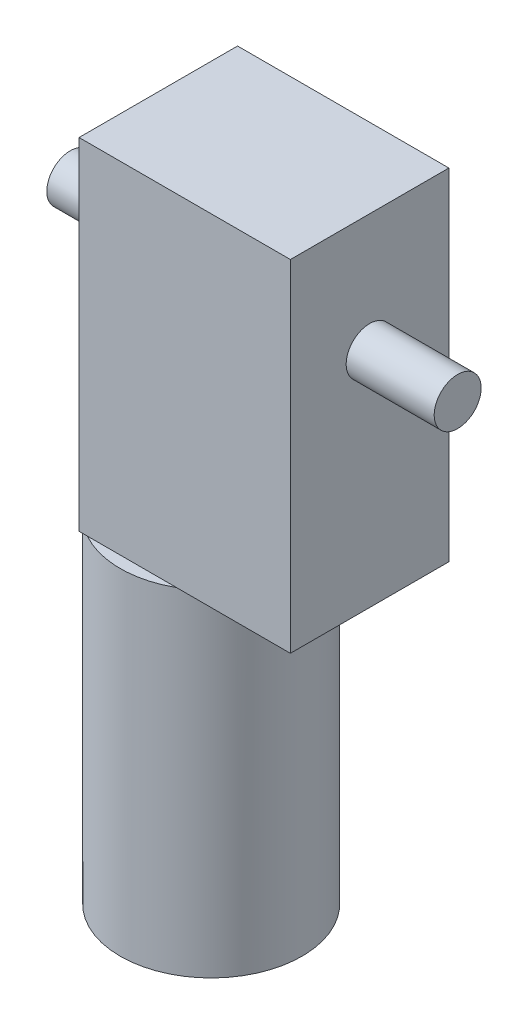
SolidWorks part; units mm, degrees
ref_plane "Front Plane" through (0, 0, 0) normal (0, 0, 1) x (1, 0, 0)
ref_plane "Top Plane" through (0, 0, 0) normal (0, 1, 0) x (1, 0, 0)
ref_plane "Right Plane" through (0, 0, 0) normal (1, 0, 0) x (0, 0, -1)
sketch "Sketch2" plane through (0, 0, 0) normal (0, 1, 0) x (1, 0, 0)
  circle A0 centre (0, 0) radius 15.494
  dimension "D1" = 30.988
extrude "Boss-Extrude1" add sketch "Sketch2" along normal blind 57.2 contours A0
sketch "Sketch3" plane through (0, 57.2, 0) normal (0, 1, 0) x (1, 0, 0)
  line L0 (0, 15.494) -> (0, -15.494) construction
  line L1 (-9, 13.5) -> (27, 13.5)
  line L2 (-9, 13.5) -> (-9, -13.5)
  line L3 (-9, -13.5) -> (27, -13.5)
  line L4 (27, 13.5) -> (27, -13.5)
  line L5 (9, 13.5) -> (9, -13.5) construction
  circle A0 centre (0, 0) radius 15.494 construction
  point P4 (9, 13.5)
  point P7 (27, 0)
  dimension "D1" = 27
  dimension "D2" = 36
  dimension "D3" = 9
extrude "Boss-Extrude2" add sketch "Sketch3" along normal blind 58.1
sketch "Sketch4" plane through (27, 0, 0) normal (1, 0, 0) x (0, 0, -1)
  line L1 (-13.5, 57.2) -> (13.5, 57.2) construction
  circle A0 centre (0, 95.1) radius 4
  dimension "D1" = 37.9
  dimension "D2" = 8
extrude "Boss-Extrude3" add sketch "Sketch4" along normal blind 15 and the other way blind 51
